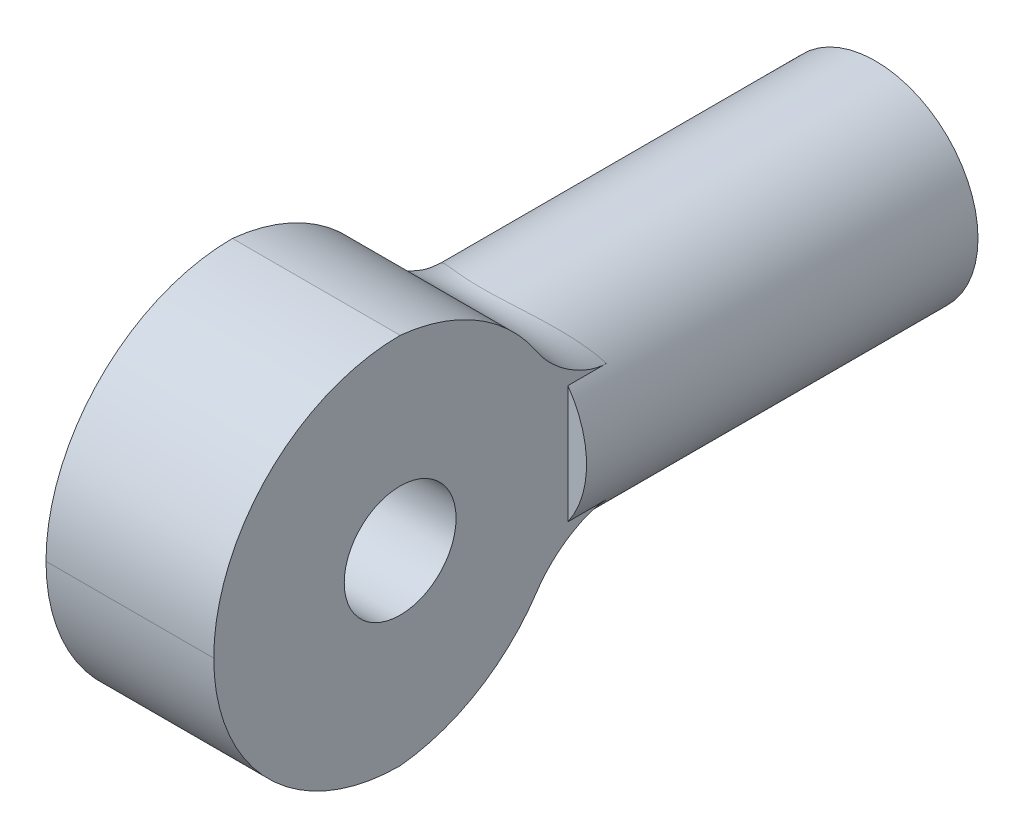
SolidWorks part; units mm, degrees
ref_plane "Front" through (0, 0, 0) normal (0, 0, 1) x (1, 0, 0)
ref_plane "Top" through (0, 0, 0) normal (0, 1, 0) x (1, 0, 0)
ref_plane "Right" through (0, 0, 0) normal (1, 0, 0) x (0, 0, -1)
sketch "Esquisse1" plane through (0, 0, 0) normal (0, 0, 1) x (1, 0, 0)
  circle A0 centre (0, 0) radius 5.5
  dimension "D1" = 11
extrude "Boss.-Extru.1" add sketch "Esquisse1" along normal blind 21
sketch "Esquisse2" plane through (0, 0, 21) normal (0, 0, 1) x (1, 0, 0)
  line L0 (0, -10) -> (0, 10) construction
  line L1 (-4.5, 0) -> (4.5, 0) construction
  line L2 (4.5, -10) -> (4.5, 10)
  line L3 (4.5, 10) -> (-4.5, 10)
  line L4 (-4.5, -10) -> (-4.5, 10)
  line L5 (4.5, -10) -> (-4.5, -10)
  point P8 (0, 0)
  dimension "D1" = 9
  dimension "D2" = 10
extrude "Boss.-Extru.2" add sketch "Esquisse2" along normal blind 19
fillet "Congé1" radius 10 2 edges at (0, -10, 40) (0, 10, 40)
sketch "Esquisse3" plane through (4.5, 0, 0) normal (1, 0, 0) x (0, 0, -1)
  circle A0 centre (-30, 0) radius 3
  dimension "D1" = 6
extrude "Enlèv. mat.-Extru.1" cut sketch "Esquisse3" against normal through all both and the other way through all
fillet "Congé2" radius 10 2 edges at (0, -10, 21) (0, 10, 21)
sketch "Esquisse4" plane through (0, 0, 0) normal (0, 0, -1) x (-1, 0, 0)
  circle A0 centre (0, 0) radius 3
  dimension "D1" = 6
extrude "Enlèv. mat.-Extru.2" cut sketch "Esquisse4" against normal blind 15
fillet "Congé3" radius 3 2 edges at (0, -5.5, 22.6156) (0, 5.5, 22.6156)
